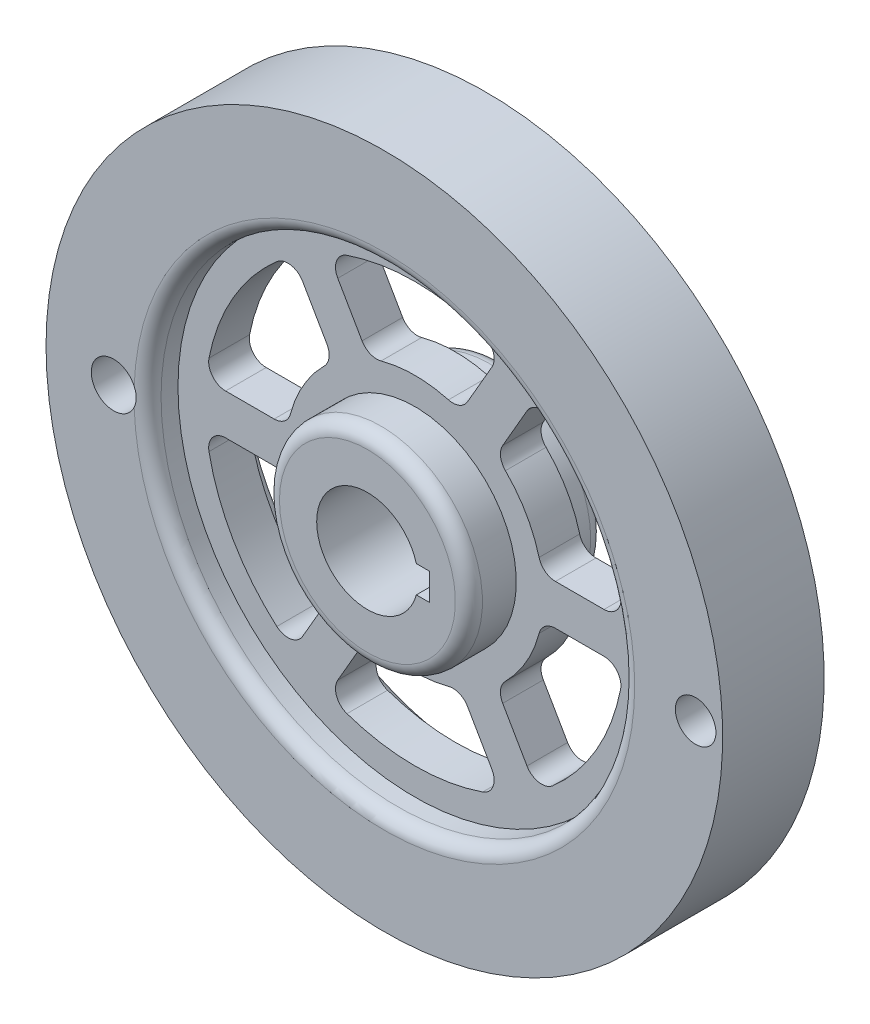
SolidWorks part; units mm, degrees
ref_plane "前视基准面" through (0, 0, 0) normal (0, 0, 1) x (1, 0, 0)
ref_plane "上视基准面" through (0, 0, 0) normal (0, 1, 0) x (1, 0, 0)
ref_plane "右视基准面" through (0, 0, 0) normal (1, 0, 0) x (0, 0, -1)
sketch "草图1" plane through (0, 0, 0) normal (0, 1, 0) x (1, 0, 0)
  line L0 (0, 20) -> (0, -20) construction
  line L1 (15, 20) -> (30, 20)
  line L2 (30, 20) -> (30, 6)
  line L3 (30, 6) -> (70, 6)
  line L4 (70, 6) -> (70, 15)
  line L5 (70, 15) -> (100, 15)
  line L6 (100, 15) -> (100, -15)
  line L7 (100, -15) -> (70, -15)
  line L8 (70, -15) -> (70, -6)
  line L9 (70, -6) -> (30, -6)
  line L10 (30, -6) -> (30, -20)
  line L11 (30, -20) -> (15, -20)
  line L12 (15, -20) -> (15, 20)
revolve "旋转1" add sketch "草图1" angle 360 about L0
ref_plane "基准面1" through (0, 0, 20) normal (0, 0, 1) x (1, 0, 0)
fillet "圆角1" radius 4 4 edges at (-70, 0, -15) (-70, 0, 15) (-30, 0, -20) (-30, 0, 20)
sketch "草图8" plane through (0, 0, 0) normal (0, 0, 1) x (1, 0, 0)
  line L0 (37.5233, 6) -> (61.709, 6)
  line L1 (36.0505, 50.44) -> (23.9577, 29.4952)
  arc A0 (61.709, 6) -> (36.0505, 50.44) centre (0.0008, -0.0014) ccw
  arc A1 (23.9577, 29.4952) -> (37.5233, 6) centre (-0.0046, -0.0039) cw
extrude "切除-拉伸10" cut sketch "草图8" against normal mid plane 402
ref_axis "基准轴1" through (0, 0, 22) along (0, 0, -1)
pattern_circular "阵列(圆周)1" count 6 over 360 about axis through (0, 0, 22) along (0, 0, -1) of "切除-拉伸10"
fillet "圆角2" radius 5 24 edges at (37.5224, -6.0004, 0) (61.7076, -6.0006, 0) (36.0507, -50.4416, 0) (23.9578, -29.4961, 0) (13.5647, -35.4956, 0) (25.6571, -56.4406, 0) (-25.6583, -56.4416, 0) (-13.5655, -35.4961, 0) (-23.9577, -29.4952, 0) (-36.0505, -50.44, 0) (-61.709, -6, 0) (-37.5233, -6, 0) (-37.5224, 6.0004, 0) (-61.7076, 6.0006, 0) (-36.0507, 50.4416, 0) (-23.9578, 29.4961, 0) (-13.5647, 35.4956, 0) (-25.6571, 56.4406, 0) (25.6583, 56.4416, 0) (13.5655, 35.4961, 0) (23.9577, 29.4952, 0) (36.0505, 50.44, 0) (61.709, 6, 0) (37.5233, 6, 0) tangent propagation no
sketch "草图10" plane through (0, 0, 0) normal (0, 0, 1) x (1, 0, 0)
  line L0 (12, -4) -> (18.3, -4)
  line L1 (18.3, -4) -> (18.3, 4)
  line L2 (18.3, 4) -> (12, 4)
  line L3 (12, 4) -> (12, -4)
extrude "切除-拉伸13" cut sketch "草图10" against normal mid plane 402
sketch "草图11" plane through (0, 0, 0) normal (0, 0, 1) x (1, 0, 0)
  circle A0 centre (-80, 0) radius 6.6218
extrude "切除-拉伸14" cut sketch "草图11" against normal mid plane 402
sketch "草图12" plane through (0, 0, 0) normal (0, 0, 1) x (1, 0, 0)
  circle A0 centre (92, 0) radius 6
extrude "切除-拉伸15" cut sketch "草图12" against normal mid plane 402
